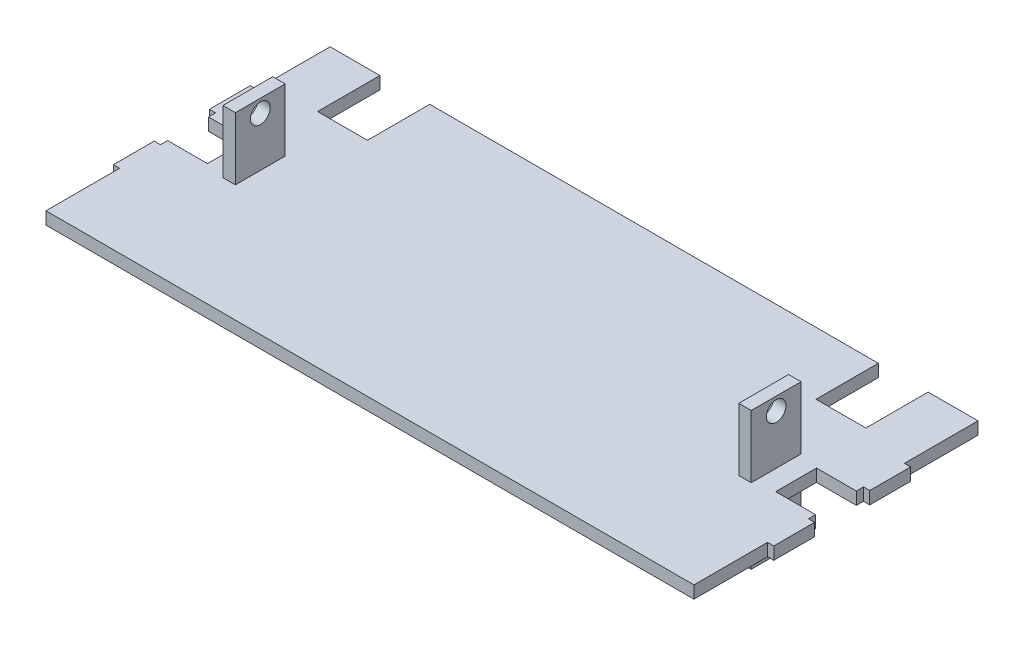
SolidWorks part; units mm, degrees
ref_plane "Front Plane" through (0, 0, 0) normal (0, 0, 1) x (1, 0, 0)
ref_plane "Top Plane" through (0, 0, 0) normal (0, 1, 0) x (1, 0, 0)
ref_plane "Right Plane" through (0, 0, 0) normal (1, 0, 0) x (0, 0, -1)
sketch "Sketch1" plane through (0, 0, 0) normal (0, 1, 0) x (1, 0, 0)
  line L0 (0, 72.39) -> (0, -72.39) construction
  line L1 (165.1, -72.39) -> (-165.1, -72.39)
  line L2 (165.1, -72.39) -> (165.1, -34.8747)
  line L3 (165.1, 72.39) -> (139.7, 72.39)
  line L4 (-165.1, -72.39) -> (-165.1, -34.8747)
  line L5 (165.1, -72.39) -> (-165.1, 72.39) construction
  line L6 (165.1, 72.39) -> (-165.1, -72.39) construction
  line L7 (165.1, 10.414) -> (144.78, 10.414)
  line L9 (165.1, -10.414) -> (144.78, -10.414)
  line L10 (144.78, 10.414) -> (144.78, -10.414)
  line L11 (-139.7, 72.39) -> (-165.1, 72.39)
  line L13 (-165.1, -10.414) -> (-144.78, -10.414)
  line L14 (-144.78, 10.414) -> (-144.78, -10.414)
  line L15 (-165.1, 10.414) -> (-144.78, 10.414)
  line L17 (-127, 0) -> (127, 0) construction
  line L18 (-165.1, 14.0467) -> (-168.275, 14.0467)
  line L20 (-165.1, 34.8747) -> (-168.275, 34.8747)
  line L21 (-168.275, 14.0467) -> (-168.275, 34.8747)
  line L22 (-165.1, -34.8747) -> (-168.275, -34.8747)
  line L23 (-168.275, -14.0467) -> (-168.275, -34.8747)
  line L24 (-165.1, -14.0467) -> (-168.275, -14.0467)
  line L27 (165.1, -14.0467) -> (168.275, -14.0467)
  line L28 (168.275, -14.0467) -> (168.275, -34.8747)
  line L29 (165.1, -34.8747) -> (168.275, -34.8747)
  line L30 (165.1, 34.8747) -> (168.275, 34.8747)
  line L31 (168.275, 14.0467) -> (168.275, 34.8747)
  line L32 (165.1, 14.0467) -> (168.275, 14.0467)
  line L34 (-165.1, 34.8747) -> (-165.1, 72.39)
  line L35 (-165.1, -14.0467) -> (-165.1, -10.414)
  line L36 (165.1, 34.8747) -> (165.1, 72.39)
  line L37 (165.1, -14.0467) -> (165.1, -10.414)
  line L38 (-165.1, 10.414) -> (-165.1, 14.0467)
  line L39 (165.1, 10.414) -> (165.1, 14.0467)
  line L40 (-139.7, 72.39) -> (-139.7, 40.64)
  line L41 (-139.7, 40.64) -> (-114.3, 40.64)
  line L42 (-114.3, 72.39) -> (-114.3, 40.64)
  line L44 (114.3, 72.39) -> (114.3, 40.64)
  line L45 (114.3, 40.64) -> (139.7, 40.64)
  line L46 (139.7, 72.39) -> (139.7, 40.64)
  line L47 (114.3, 72.39) -> (-114.3, 72.39)
  point P0 (0, 0)
  point P6 (127, 0)
  dimension "D1" = 330.2
  dimension "D2" = 144.78
  dimension "D3" = 20.828
  dimension "D5" = 3.175
  dimension "D6" = 20.828
  dimension "D4" = 20.32
  dimension "D7" = 31.75
  dimension "D8" = 25.4
  dimension "D9" = 25.4
  dimension "D10" = 31.75
  dimension "D12" = 25.4
  dimension "D11" = 25.4
extrude "Boss-Extrude1" add sketch "Sketch1" along normal mid plane 6.35
sketch "Sketch2" plane through (0, 0, 0) normal (0, 1, 0) x (1, 0, 0)
  line L0 (-144.78, 10.414) -> (-144.78, -10.414) construction
  line L1 (128.27, -12.7) -> (134.62, -12.7)
  line L2 (128.27, -12.7) -> (128.27, 12.7)
  line L3 (128.27, 12.7) -> (134.62, 12.7)
  line L4 (134.62, -12.7) -> (134.62, 12.7)
  line L5 (128.27, -12.7) -> (134.62, 12.7) construction
  line L6 (128.27, 12.7) -> (134.62, -12.7) construction
  line L9 (-128.27, -12.7) -> (-128.27, 12.7)
  line L10 (-128.27, 12.7) -> (-134.62, 12.7)
  line L11 (-134.62, -12.7) -> (-134.62, 12.7)
  line L12 (-128.27, -12.7) -> (-134.62, -12.7)
  line L13 (144.78, -10.414) -> (144.78, 10.414) construction
  point P0 (131.445, 0)
  point P10 (144.78, 0)
  dimension "D1" = 10.16
  dimension "D2" = 10.16
  dimension "D3" = 25.4
  dimension "D4" = 25.4
  dimension "D5" = 6.35
  dimension "D6" = 6.35
  dimension "D7" = 6.35
extrude "Boss-Extrude2" add sketch "Sketch2" along normal mid plane 70.104
sketch "Sketch3" plane through (-134.62, 0, 0) normal (-1, 0, 0) x (0, 0, 1)
  circle A0 centre (0, 28.4406) radius 5.0038
  circle A1 centre (0, -28.4406) radius 5.0038
  dimension "D1" = 10.0076
  dimension "D2" = 10.0076
extrude "Cut-Extrude1" cut sketch "Sketch3" against normal through all both and the other way through all
equation "\"length\"=13"
equation "\"width\"= 5.7"
equation "\"height\"= 0.25"
equation "\"D1@Sketch1\"=\"length\""
equation "\"D2@Sketch1\"=\"width\""
equation "\"eyebolt width\"= 0.82"
equation "\"eyebolt length\"= 0.8"
equation "\"D3@Sketch1\"=\"eyebolt width\""
equation "\"D4@Sketch1\"=\"eyebolt length\""
equation "\"lead screw holder height\"= 2.76"
equation "\"lead screw diameter\"=0.394"
equation "\"D1@Sketch3\"=\"lead screw diameter\""
equation "\"distance from holders to board\"=0.4"
equation "\"D2@Sketch3\"=\"lead screw diameter\""
